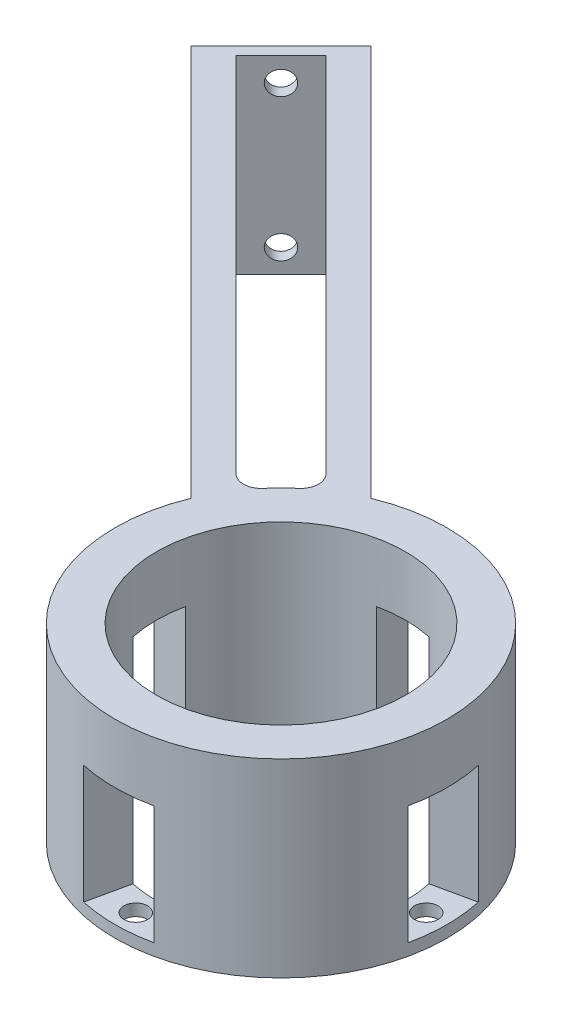
SolidWorks part; units mm, degrees
ref_plane "Front Plane" through (0, 0, 0) normal (0, 0, 1) x (1, 0, 0)
ref_plane "Top Plane" through (0, 0, 0) normal (0, 1, 0) x (1, 0, 0)
ref_plane "Right Plane" through (0, 0, 0) normal (1, 0, 0) x (0, 0, -1)
sketch "草图1" plane through (0, 0, 0) normal (0, 1, 0) x (1, 0, 0)
  circle A1 centre (-24.5, 0) radius 2
  circle A2 centre (0, 24.5) radius 2
  circle A3 centre (24.5, 0) radius 2
  circle A4 centre (0, -24.5) radius 2
  circle A5 centre (0, 0) radius 21
  circle A6 centre (0, 0) radius 28
  dimension "D1" = 4
extrude "凸台-拉伸1" add sketch "草图1" along normal blind 2
sketch "草图2" plane through (0, 2, 0) normal (0, 1, 0) x (1, 0, 0)
  line L0 (0, 0) -> (14.8492, 14.8492)
  line L1 (4.4515, 20.5228) -> (5.9354, 27.3637)
  line L2 (20.5228, 4.4515) -> (27.3637, 5.9354)
  line L3 (20.5228, -4.4515) -> (27.3637, -5.9354)
  line L4 (4.4515, -20.5228) -> (5.9354, -27.3637)
  line L5 (-4.4515, -20.5228) -> (-5.9354, -27.3637)
  line L6 (-20.5228, -4.4515) -> (-27.3637, -5.9354)
  line L7 (-20.5228, 4.4515) -> (-27.3637, 5.9354)
  line L8 (-4.4515, 20.5228) -> (-5.9354, 27.3637)
  arc A0 (20.5228, 4.4515) -> (4.4515, 20.5228) centre (0, 0) ccw
  arc A1 (27.3637, 5.9354) -> (5.9354, 27.3637) centre (0, 0) ccw
  circle A2 centre (0, 0) radius 21 construction
  circle A3 centre (0, 0) radius 28 construction
  arc A4 (5.9354, -27.3637) -> (27.3637, -5.9354) centre (0, 0) ccw
  arc A5 (4.4515, -20.5228) -> (20.5228, -4.4515) centre (0, 0) ccw
  arc A6 (-27.3637, -5.9354) -> (-5.9354, -27.3637) centre (0, 0) ccw
  arc A7 (-20.5228, -4.4515) -> (-4.4515, -20.5228) centre (0, 0) ccw
  arc A8 (-5.9354, 27.3637) -> (-27.3637, 5.9354) centre (0, 0) ccw
  arc A9 (-4.4515, 20.5228) -> (-20.5228, 4.4515) centre (0, 0) ccw
  dimension "D1" = 4
extrude "凸台-拉伸3" add sketch "草图2" along normal blind 30 contours L8 L7 | L4 L3 | L6 L5 | L1 A1 L2 A0 region at (16.5069, 2, 16.5069) region at (-16.5069, 2, 16.5069) region at (-16.5069, 2, -16.5069)
sketch "草图5" plane through (0, 32, 0) normal (0, 1, 0) x (1, 0, 0)
  circle A0 centre (0, 0) radius 21
  circle A1 centre (0, 0) radius 28
extrude "凸台-拉伸4" add sketch "草图5" against normal blind 10
ref_point "点1"
ref_point "点2"
ref_axis "基准轴3" through (0, 2, -24.5) along (0, -1, 0)
ref_plane "基准面1" through (-12.25, 0, -12.25) normal (-0.7071, 0, -0.7071) x (-0.7071, 0, 0.7071)
sketch "草图6" plane through (-12.25, 0, -12.25) normal (-0.7071, 0, -0.7071) x (-0.7071, 0, 0.7071)
  line L0 (-10.7206, 0) -> (-5.3603, 0)
  line L1 (-10.7206, 0) -> (-10.7206, 32)
  line L2 (0, 0) -> (0, 23.4994)
  line L3 (10.7206, 0) -> (10.7206, 32)
  line L6 (-5.3603, 0) -> (-5.3603, 32)
  line L7 (5.3603, 0) -> (5.3603, 32)
  line L8 (5.3603, 0) -> (10.7206, 0)
  line L9 (10.7206, 32) -> (5.3603, 32)
  line L10 (-5.3603, 32) -> (-10.7206, 32)
extrude "凸台-拉伸6" add sketch "草图6" along normal blind 100 contours L6 L10 L1 L0 | L3 L9 L7 L8
sketch "草图9" plane through (0, 0, 0) normal (0, -1, 0) x (1, 0, 0)
  circle A0 centre (0, 0) radius 21
extrude "切除-拉伸1" cut sketch "草图9" against normal blind 32
sketch "草图11" plane through (-82.9607, 0, -82.9607) normal (-0.7071, 0, -0.7071) x (-0.7071, 0, 0.7071)
  line L0 (10.7206, 16) -> (-10.7206, 16)
  line L1 (10.7206, 0) -> (-10.7206, 0)
  line L2 (10.7206, 0) -> (10.7206, 32)
  line L3 (10.7206, 32) -> (-10.7206, 32)
  line L4 (-10.7206, 0) -> (-10.7206, 32)
  line L5 (0, 4) -> (0, 28)
  circle A0 centre (0, 4) radius 2
  circle A1 centre (0, 28) radius 2
  line M5 (10.7206, 0) -> (10.7206, 32)
  line M6 (10.7206, 32) -> (5.3603, 32)
  line M7 (5.3603, 32) -> (5.3603, 0)
  line M8 (5.3603, 0) -> (10.7206, 0)
extrude "凸台-拉伸7" add sketch "草图11" along normal blind 2 contours L4 L1 L0 A0 M7 | L0 M5 M7 M8 | L0 M5 M6 M7 | L4 L0 L3 A1 M7 region at (-88.6461, 8, -77.2752) region at (-88.6461, 24, -77.2752) region at (-80.9682, 8.2054, -84.9531) region at (-80.9682, 23.7946, -84.9531)
fillet "圆角1" radius 3 2 edges at (-15.6425, 16, -23.2231) (-23.2231, 16, -15.6425)
